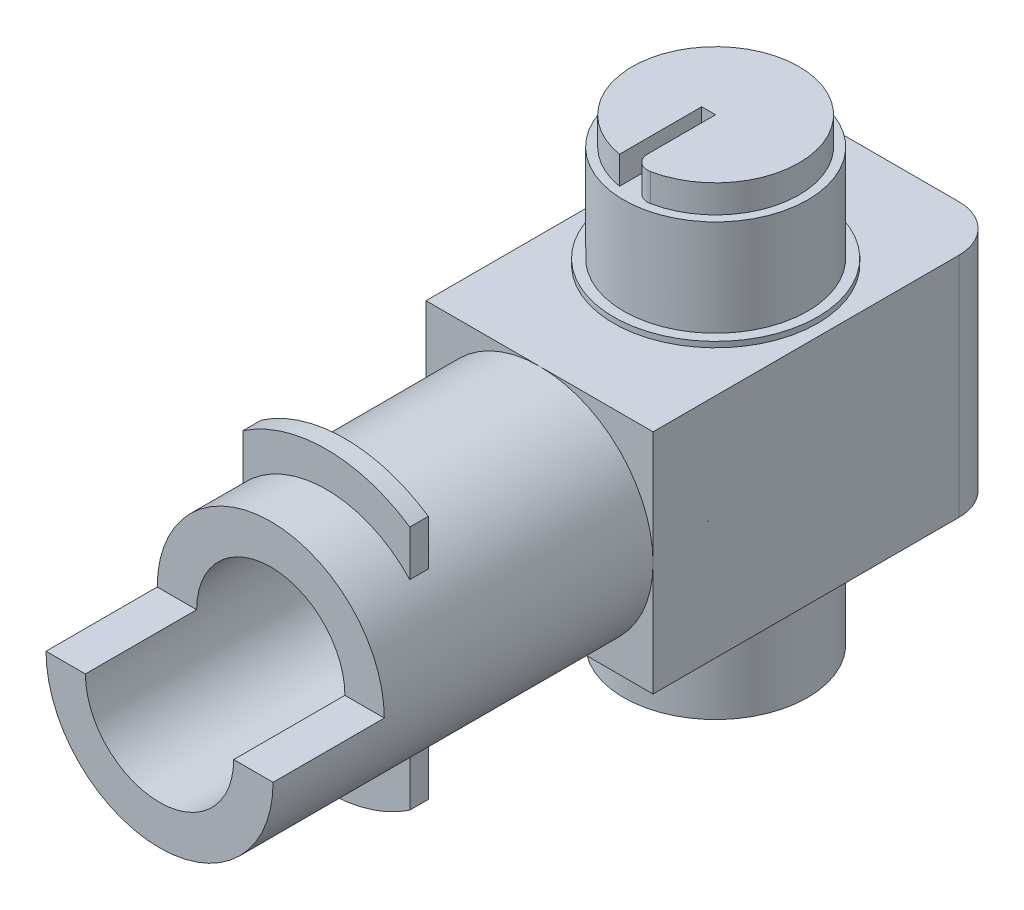
SolidWorks part; units mm, degrees
ref_plane "前视基准面" through (0, 0, 0) normal (0, 0, 1) x (1, 0, 0)
ref_plane "上视基准面" through (0, 0, 0) normal (0, 1, 0) x (1, 0, 0)
ref_plane "右视基准面" through (0, 0, 0) normal (1, 0, 0) x (0, 0, -1)
sketch "草图3" plane through (0, 0, 0) normal (0, 0, 1) x (1, 0, 0)
  circle A0 centre (0, 0) radius 12.25
  circle A1 centre (0, 0) radius 8
  dimension "D1" = 16
  dimension "D2" = 24.5
extrude "凸台-拉伸1" add sketch "草图3" along normal blind 23
ref_plane "基准面1" through (0, 0, 3) normal (0, 0, -1) x (-1, 0, 0)
sketch "草图4" plane through (0, 0, 3) normal (0, 0, -1) x (-1, 0, 0)
  line L0 (0, 0) -> (9, 0) construction
  line L1 (9, 0) -> (9, 13.2288)
  line L2 (9, 0) -> (9, -13.2288)
  line L3 (0, 0) -> (0, 6.1164) construction
  line L4 (-9, 0) -> (-9, -13.2288)
  line L5 (-9, 0) -> (-9, 13.2288)
  circle A0 centre (0, 0) radius 8
  arc A1 (9, 13.2288) -> (-9, 13.2288) centre (0, 0) ccw
  arc A2 (-9, -13.2288) -> (9, -13.2288) centre (0, 0) ccw
  dimension "D1" = 16
  dimension "D2" = 32
  dimension "D3" = 9
extrude "凸台-拉伸2" add sketch "草图4" against normal blind 2
ref_plane "基准面2" through (0, 0, 23) normal (0, 0, 1) x (1, 0, 0)
sketch "草图5" plane through (0, 0, 23) normal (0, 0, 1) x (1, 0, 0)
  line L0 (0, 0) -> (16.1924, 0)
  line L1 (16.1924, 0) -> (16.1924, 15.4379)
  line L2 (16.1924, 15.4379) -> (-18.0643, 15.4379)
  line L3 (-18.0643, 15.4379) -> (-18.0643, 0)
  line L4 (-18.0643, 0) -> (0, 0)
  dimension "D1" = 34.2566
  dimension "D2" = 15.4379
  dimension "D3" = 16.1924
extrude "切除-拉伸1" cut sketch "草图5" against normal blind 12
extrude "凸台-拉伸3" add sketch "草图3<2>" against normal blind 18
sketch "草图3<2>" plane through (0, 0, 0) normal (0, 0, 1) x (1, 0, 0) same geometry as "草图3"
ref_plane "基准面3" through (0, 0, -18) normal (0, 0, -1) x (-1, 0, 0)
sketch "草图6" plane through (0, 0, -18) normal (0, 0, -1) x (-1, 0, 0)
  line L1 (12.25, 12.25) -> (-12.25, 12.25)
  line L2 (12.25, 12.25) -> (12.25, -12.25)
  line L3 (12.25, -12.25) -> (-12.25, -12.25)
  line L4 (-12.25, 12.25) -> (-12.25, -12.25)
  point P4 (0, 0)
  dimension "D1" = 12.25
  dimension "D2" = 12.25
  dimension "D3" = 24.5
  dimension "D4" = 24.5
extrude "凸台-拉伸4" add sketch "草图6" along normal blind 38
sketch "草图8" plane through (0, 0, -18) normal (0, 0, -1) x (-1, 0, 0)
  circle A0 centre (0, 0) radius 8
  dimension "D1" = 16
extrude "切除-拉伸2" cut sketch "草图8" along normal blind 38
ref_plane "基准面4" through (0, -12.25, 0) normal (0, -1, 0) x (-1, 0, 0)
sketch "草图9" plane through (0, -12.25, 0) normal (0, -1, 0) x (-1, 0, 0)
  line L0 (0, 18) -> (0, 56) construction
  line L1 (-12.25, 56) -> (12.25, 56) construction
  circle A0 centre (0, 37) radius 9.925
  dimension "D1" = 19.85
extrude "凸台-拉伸6" add sketch "草图9" along normal blind 11 contours A0
sketch "草图10" plane through (0, -12.25, 0) normal (0, -1, 0) x (-1, 0, 0)
  line L0 (0, 56) -> (0, 18) construction
  line L1 (-12.25, 56) -> (12.25, 56) construction
  circle A0 centre (0, 37) radius 11
  dimension "D1" = 22
extrude "凸台-拉伸7" add sketch "草图10" along normal blind 0.6
ref_plane "基准面5" through (0, 0, 0) normal (0, -1, 0) x (-1, 0, 0)
mirror "镜向1" about plane through (0, 0, 0) normal (0, -1, 0) of "凸台-拉伸7", "凸台-拉伸6"
ref_plane "基准面6" through (0, 23.25, 0) normal (0, 1, 0) x (1, 0, 0)
sketch "草图11" plane through (0, 23.25, 0) normal (0, 1, 0) x (1, 0, 0)
  line L1 (0, 37) -> (0, 29.6515)
  line L2 (0, 37) -> (-1.5, 37)
  line L3 (-1.5, 37) -> (-1.5, 28.1259)
  arc A0 (1.8, 28.1818) -> (-1.5, 28.1259) centre (0, 37) ccw
  arc A1 (0, 29.6515) -> (1.8, 28.1818) centre (1.5, 29.6515) ccw
  dimension "D1" = 18
  dimension "D3" = 1.5
  dimension "D2" = 1.5
extrude "凸台-拉伸8" add sketch "草图11" along normal blind 3
ref_plane "基准面7" through (0, -23.25, 0) normal (0, -1, 0) x (-1, 0, 0)
sketch "草图12" plane through (0, -23.25, 0) normal (0, -1, 0) x (-1, 0, 0)
  line L1 (1.25, 35.4388) -> (1.25, 38.5612)
  line L3 (-1.25, 35.4388) -> (-1.25, 38.5612)
  arc A0 (-1.25, 35.4388) -> (1.25, 35.4388) centre (0, 37) ccw
  arc A1 (1.25, 38.5612) -> (-1.25, 38.5612) centre (0, 37) ccw
  dimension "D1" = 4
  dimension "D2" = 1.25
  dimension "D4" = 1.25
extrude "切除-拉伸3" cut sketch "草图12" against normal blind 5.5 contours L3 A1 L1 A0
fillet "圆角5" radius 5 2 edges at (-12.25, 0, -56) (12.25, 0, -56)
